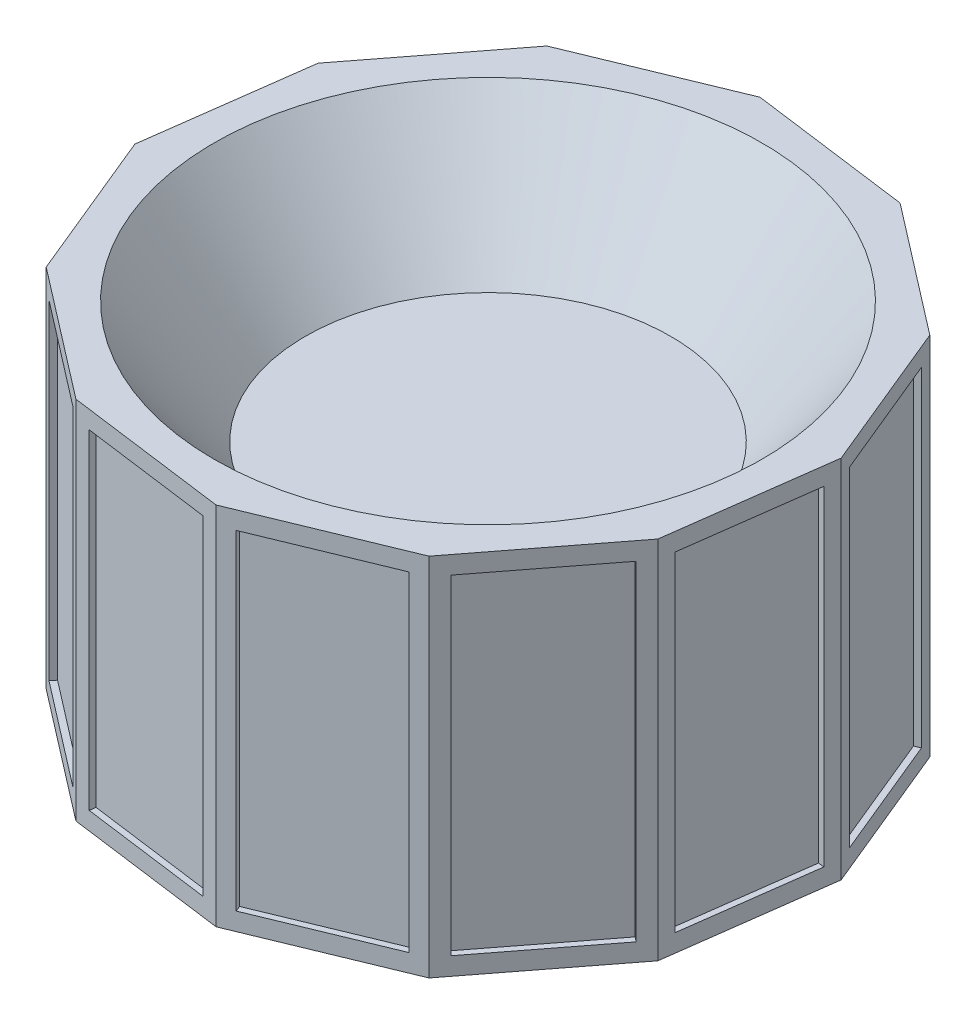
SolidWorks part; units mm, degrees
ref_plane "前视基准面" through (0, 0, 0) normal (0, 0, 1) x (1, 0, 0)
ref_plane "上视基准面" through (0, 0, 0) normal (0, 1, 0) x (1, 0, 0)
ref_plane "右视基准面" through (0, 0, 0) normal (1, 0, 0) x (0, 0, -1)
ref_plane "基准面1" through (0, -1025, 0) normal (0, 1, 0) x (-1, 0, 0)
sketch "草图1" plane through (0, -1025, 0) normal (0, 1, 0) x (-1, 0, 0)
  circle A0 centre (0, 0) radius 50
  circle A1 centre (0, 0) radius 90
  dimension "D1" = 100
  dimension "D2" = 180
extrude "凸台-拉伸1" add sketch "草图1" along normal mid plane 100
ref_plane "基准面2" through (0, -875, 0) normal (0, 1, 0) x (-1, 0, 0)
ref_plane "基准面3" through (0, -1175, 0) normal (0, 1, 0) x (-1, 0, 0)
sketch "草图4" plane through (0, -1175, 0) normal (0, 1, 0) x (-1, 0, 0)
  line L1 (157.2152, -205.5983) -> (238.9515, -99.4458)
  line L2 (238.9515, -99.4458) -> (256.661, 33.3532)
  line L3 (256.661, 33.3532) -> (205.5983, 157.2152)
  line L4 (205.5983, 157.2152) -> (99.4458, 238.9515)
  line L5 (99.4458, 238.9515) -> (-33.3532, 256.661)
  line L6 (-33.3532, 256.661) -> (-157.2152, 205.5983)
  line L7 (-157.2152, 205.5983) -> (-238.9515, 99.4458)
  line L8 (-238.9515, 99.4458) -> (-256.661, -33.3532)
  line L9 (-256.661, -33.3532) -> (-205.5983, -157.2152)
  line L10 (-205.5983, -157.2152) -> (-99.4458, -238.9515)
  line L11 (-99.4458, -238.9515) -> (33.3532, -256.661)
  line L12 (33.3532, -256.661) -> (157.2152, -205.5983)
  circle A0 centre (0, 0) radius 250 construction
  dimension "D1" = 500
ref_plane "基准面4" through (0, -975, 0) normal (0, 1, 0) x (-1, 0, 0)
ref_plane "基准面5" through (0, -1075, 0) normal (0, 1, 0) x (-1, 0, 0)
sketch "草图5" plane through (0, -975, 0) normal (0, 1, 0) x (-1, 0, 0)
  circle A0 centre (0, 0) radius 150
  dimension "D1" = 300
sketch "草图6" plane through (0, -1075, 0) normal (0, 1, 0) x (-1, 0, 0)
  circle A0 centre (0, 0) radius 150
  dimension "D1" = 300
extrude "凸台-拉伸2" add sketch "草图5" against normal blind 100
sketch "草图8" plane through (0, -1175, 0) normal (0, 1, 0) x (-1, 0, 0)
  circle A0 centre (0, 0) radius 225
  dimension "D1" = 450
extrude "凸台-拉伸4" add sketch "草图4" along normal blind 300
loft "切除-放样3" cut profiles "草图6", "草图8" connector at (0, -1075, 150) connector at (0, -1175, 225)
mirror "镜向2" about plane through (0, -1025, 0) normal (0, 1, 0) of "切除-放样3"
sketch "草图9" plane through (231.1297, 0, -95.2842) normal (0.9245, 0, -0.3811) x (-0.3811, 0, -0.9245)
  line L0 (-66.9873, -1175) -> (66.9873, -875)
  line L2 (54.2971, -1160.3404) -> (-54.2971, -1160.3404)
  line L3 (54.2971, -1160.3404) -> (54.2971, -889.6596)
  line L4 (-66.9873, -1175) -> (66.9873, -1175)
  line L5 (66.9873, -1175) -> (66.9873, -875)
  line L6 (66.9873, -875) -> (-66.9873, -875)
  line L7 (-66.9873, -875) -> (-66.9873, -1175)
  line L8 (-66.9873, -1175) -> (66.9873, -1175)
  line L9 (66.9873, -1175) -> (66.9873, -875)
  line L10 (66.9873, -875) -> (-66.9873, -875)
  line L11 (-66.9873, -875) -> (-66.9873, -1175)
  line L12 (54.2971, -889.6596) -> (-54.2971, -889.6596)
  line L13 (-54.2971, -1160.3404) -> (-54.2971, -889.6596)
  line L14 (54.2971, -1160.3404) -> (-54.2971, -889.6596) construction
  line L15 (54.2971, -889.6596) -> (-54.2971, -1160.3404) construction
  point P2 (0, -1025)
  dimension "D1" = 0
extrude "切除-拉伸1" cut sketch "草图9" against normal blind 5 contours L13 L0 L3 L12 | L13 L2 L3 L0 region at (237.3267, -975.534, -80.2521) region at (224.9326, -1074.466, -110.3163)
pattern_circular "阵列(圆周)1" count 12 over 360 about axis through (0, -1175, 0) along (0, 1, 0) of "切除-拉伸1"
